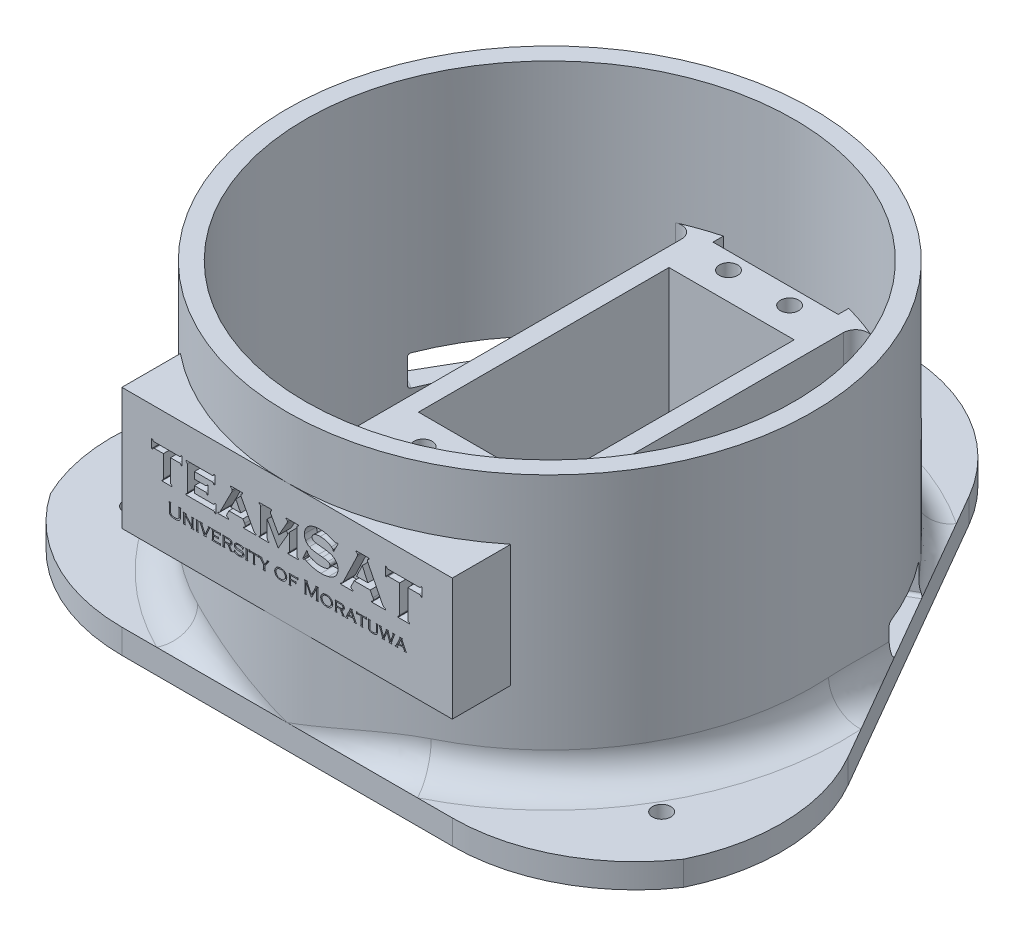
SolidWorks part; units mm, degrees
ref_plane "Front Plane" through (0, 0, 0) normal (0, 0, 1) x (1, 0, 0)
ref_plane "Top Plane" through (0, 0, 0) normal (0, 1, 0) x (1, 0, 0)
ref_plane "Right Plane" through (0, 0, 0) normal (1, 0, 0) x (0, 0, -1)
sketch "Sketch1" plane through (0, 0, 0) normal (0, 1, 0) x (1, 0, 0)
  line L0 (0, 0) -> (0, -11.25) construction
  line L1 (0, -40) -> (0, -43) construction
  line L2 (0, 0) -> (40, 0) construction
  line L3 (10.25, 38.6644) -> (10.25, 36.95)
  line L4 (-10.25, 38.6644) -> (-10.25, 36.95)
  line L5 (13.25, 37.7417) -> (13.25, -37.7417)
  line L6 (-13.25, 37.7417) -> (-13.25, -37.7417)
  line L7 (-10.25, 29.75) -> (10.25, 29.75)
  line L8 (10.25, 36.95) -> (-10.25, 36.95)
  line L9 (-10.25, -11.25) -> (10.25, -11.25)
  line L10 (-10.25, -18.45) -> (10.25, -18.45)
  line L11 (-10.25, 29.75) -> (-10.25, -11.25)
  line L12 (10.25, 29.75) -> (10.25, -11.25)
  line L13 (-10.25, -18.45) -> (-10.25, -38.6644)
  line L14 (0, -18.45) -> (0, -40) construction
  line L15 (10.25, -18.45) -> (10.25, -38.6644)
  arc A0 (-13.25, 37.7417) -> (-13.25, -37.7417) centre (0, 0) ccw
  circle A1 centre (0, 0) radius 43
  arc A2 (10.25, 38.6644) -> (-10.25, 38.6644) centre (0, 0) ccw
  arc A3 (-10.25, -38.6644) -> (10.25, -38.6644) centre (0, 0) ccw
  arc A4 (13.25, -37.7417) -> (13.25, 37.7417) centre (0, 0) ccw
  point P10 (10.25, 0)
  point P15 (13.25, 0)
  dimension "D1" = 80
  dimension "D2" = 10.25
  dimension "D4" = 86
  dimension "D3" = 3
  dimension "D5" = 7.2
  dimension "D6" = 7.2
  dimension "D7" = 41
  dimension "D8" = 11.25
extrude "Boss-Extrude1" add sketch "Sketch1" along normal blind 27
sketch "Sketch2" plane through (0, 27, 0) normal (0, 1, 0) x (1, 0, 0)
  line L0 (-40, 0) -> (40, 0) construction
  arc A0 (-13.25, 37.7417) -> (-13.25, -37.7417) centre (0, 0) ccw construction
  arc A1 (13.25, -37.7417) -> (13.25, 37.7417) centre (0, 0) ccw construction
  circle A2 centre (0, 0) radius 43
  circle A3 centre (0, 0) radius 40
extrude "Boss-Extrude2" add sketch "Sketch2" along normal blind 21
sketch "Sketch3" plane through (0, 0, 0) normal (0, -1, 0) x (1, 0, 0)
  line L1 (-58.1616, 14.7387) -> (-16.3168, -57.7387)
  line L4 (0, 0) -> (-51.9615, 30) construction
  line L5 (0, 0) -> (51.9615, 30) construction
  line L6 (-41.845, 43) -> (41.845, 43)
  line L7 (0, 0) -> (0, -60) construction
  line L8 (16.3168, -57.7387) -> (58.1616, 14.7387)
  line L9 (-74.4782, 43) -> (-104.0629, 60.0807) construction
  line L10 (74.4782, 43) -> (104.0629, 60.0807) construction
  line L11 (0, -86.0004) -> (0, -151.5212) construction
  circle A0 centre (0, 0) radius 40
  arc A1 (-41.845, 43) -> (-58.1616, 14.7387) centre (0, 0) ccw
  arc A2 (58.1616, 14.7387) -> (41.845, 43) centre (0, 0) ccw
  arc A3 (-16.3168, -57.7387) -> (16.3168, -57.7387) centre (0, 0) ccw
  circle A4 centre (43.3013, 25) radius 1.5
  circle A6 centre (0, -50) radius 1.5
  circle A7 centre (-43.3013, 25) radius 1.5
  dimension "D1" = 120
  dimension "D2" = 3
  dimension "D3" = 50
extrude "Boss-Extrude3" add sketch "Sketch3" against normal blind 4
fillet "Fillet1" radius 5 1 edges at (0, 4, -43)
fillet "Fillet2" radius 30 6 edges at (58.1616, 2, 14.7387) (41.845, 2, 43) (-41.845, 2, 43) (16.3168, 2, -57.7387) (-58.1616, 2, 14.7387) (-16.3168, 2, -57.7387)
fillet "Fillet3" radius 2 6 edges at (-10.25, 13.5, 18.45) (10.25, 13.5, 18.45) (13.25, 13.5, -37.7417) (13.25, 13.5, 37.7417) (-13.25, 13.5, 37.7417) (-13.25, 13.5, -37.7417)
sketch "Sketch4" plane through (0, 27, 0) normal (0, 1, 0) x (1, 0, 0)
  line L0 (0, 36.95) -> (0, -18.45) construction
  line L1 (-10.25, 36.95) -> (10.25, 36.95) construction
  line L2 (8.25, -18.45) -> (-8.25, -18.45) construction
  line L3 (-13.25, 34.25) -> (13.25, 34.25) construction
  line L4 (-13.25, -34.8057) -> (-13.25, 34.8057) construction
  line L5 (13.25, 34.8057) -> (13.25, -34.8057) construction
  line L6 (10.25, 29.75) -> (-10.25, 29.75) construction
  line L7 (-13.25, -15.75) -> (13.25, -15.75) construction
  line L8 (-10.25, -11.25) -> (10.25, -11.25) construction
  line L9 (0, 0) -> (-13.25, 0) construction
  circle A0 centre (-5, 34.25) radius 1.5
  circle A1 centre (5, 34.25) radius 1.5
  circle A2 centre (-5, -15.75) radius 1.5
  circle A3 centre (5, -15.75) radius 1.5
  dimension "D3" = 3
  dimension "D5" = 3
  dimension "D1" = 4.5
  dimension "D2" = 4.5
  dimension "D4" = 5
  dimension "D6" = 5
extrude "Cut-Extrude1" cut sketch "Sketch4" against normal through all
sketch "Sketch5" plane through (0, 0, 11.25) normal (0, 0, -1) x (-1, 0, 0)
  line L0 (10.25, 0) -> (-10.25, 0) construction
  line L1 (-5.25, 0) -> (4.75, 0)
  line L2 (-5.25, 0) -> (-5.25, 6.7409)
  line L3 (-5.25, 6.7409) -> (4.75, 6.7409)
  line L4 (4.75, 0) -> (4.75, 6.7409)
  line L5 (-10.25, 27) -> (-10.25, 0) construction
  dimension "D1" = 10
  dimension "D2" = 5
extrude "Cut-Extrude2" cut sketch "Sketch5" against normal blind 12
sketch "Sketch7" plane through (10.25, 0, 0) normal (-1, 0, 0) x (0, 0, 1)
  line L0 (20.45, 27) -> (20.45, 0) construction
  line L1 (20.45, 3.871) -> (33.45, 3.871)
  line L2 (20.45, 3.871) -> (20.45, 8.871)
  line L3 (20.45, 8.871) -> (33.45, 8.871)
  line L4 (33.45, 3.871) -> (33.45, 8.871)
  dimension "D1" = 13
  dimension "D2" = 5
extrude "Cut-Extrude3" cut sketch "Sketch7" against normal blind 10
fillet "Fillet5" radius 0.5 3 edges at (11.75, 8.871, 20.45) (11.75, 3.871, 20.45) (11.75, 3.871, 33.45)
fillet "Fillet6" radius 0.5 1 edges at (11.75, 8.871, 33.45)
sketch "Sketch8" plane through (37.2392, 0, -21.5) normal (0.866, 0, -0.5) x (-0.5, 0, -0.866)
  line L0 (21.3305, 4) -> (-21.3305, 4) construction
  line L1 (0, 4) -> (0, 13.7506) construction
  line L3 (-6.7628, 4) -> (6.2372, 4)
  line L4 (-6.7628, 4) -> (-6.7628, 9)
  line L5 (-6.7628, 9) -> (6.2372, 9)
  line L6 (6.2372, 4) -> (6.2372, 9)
  dimension "D1" = 13
  dimension "D2" = 5
extrude "Cut-Extrude4" cut sketch "Sketch8" against normal up to next
fillet "Fillet7" radius 0.5 4 edges at (38.8404, 9, -14.6154) (32.4127, 9, -25.9155) (32.6097, 4, -26.0292) (39.0722, 4, -14.7492)
sketch "Sketch9" plane through (-37.2392, 0, -21.5) normal (-0.866, 0, -0.5) x (-0.5, 0, 0.866)
  line L0 (0, 4) -> (0, 29.1179) construction
  line L1 (21.3305, 4) -> (-21.3305, 4) construction
  line L3 (-6.5, 4) -> (6.5, 4)
  line L4 (-6.5, 4) -> (-6.5, 9)
  line L5 (-6.5, 9) -> (6.5, 9)
  line L6 (6.5, 4) -> (6.5, 9)
  dimension "D1" = 13
  dimension "D2" = 6.5
  dimension "D3" = 5
extrude "Cut-Extrude5" cut sketch "Sketch9" against normal up to next
fillet "Fillet8" radius 0.5 4 edges at (-38.7459, 9, -14.8643) (-32.2459, 9, -26.1227) (-32.4599, 4, -26.2462) (-38.9599, 4, -14.9879)
sketch "Sketch11" plane through (0, 0, 43) normal (0, 0, 1) x (1, 0, 0)
  line L0 (-27.037, 4) -> (-27.037, 46.9953) construction
  line L1 (27.037, 4) -> (27.037, 45.2484) construction
  line L2 (43, 48) -> (-43, 48) construction
  line L3 (-27.037, 38) -> (27.037, 38)
  line L4 (-27.037, 38) -> (-27.037, 18)
  line L5 (-27.037, 18) -> (27.037, 18)
  line L6 (27.037, 38) -> (27.037, 18)
  dimension "D1" = 20
  dimension "D2" = 10
extrude "Boss-Extrude4" add sketch "Sketch11" against normal up to next
sketch "Sketch12" plane through (0, 0, 43) normal (0, 0, 1) x (1, 0, 0)
  line L0 (-27.037, 28) -> (27.037, 28) construction
  line L1 (-27.037, 38) -> (-27.037, 18) construction
  line L2 (27.037, 18) -> (27.037, 38) construction
  line L3 (0, 18) -> (0, 38) construction
  line L4 (-27.037, 23.6863) -> (27.037, 23.6863) construction
  text T0 "teamSAT" font "Copperplate Gothic Bold" height 6
  text T1 "University of Moratuwa" font "Copperplate Gothic Light" height 2
extrude "Cut-Extrude7" cut sketch "Sketch12" against normal blind 2
